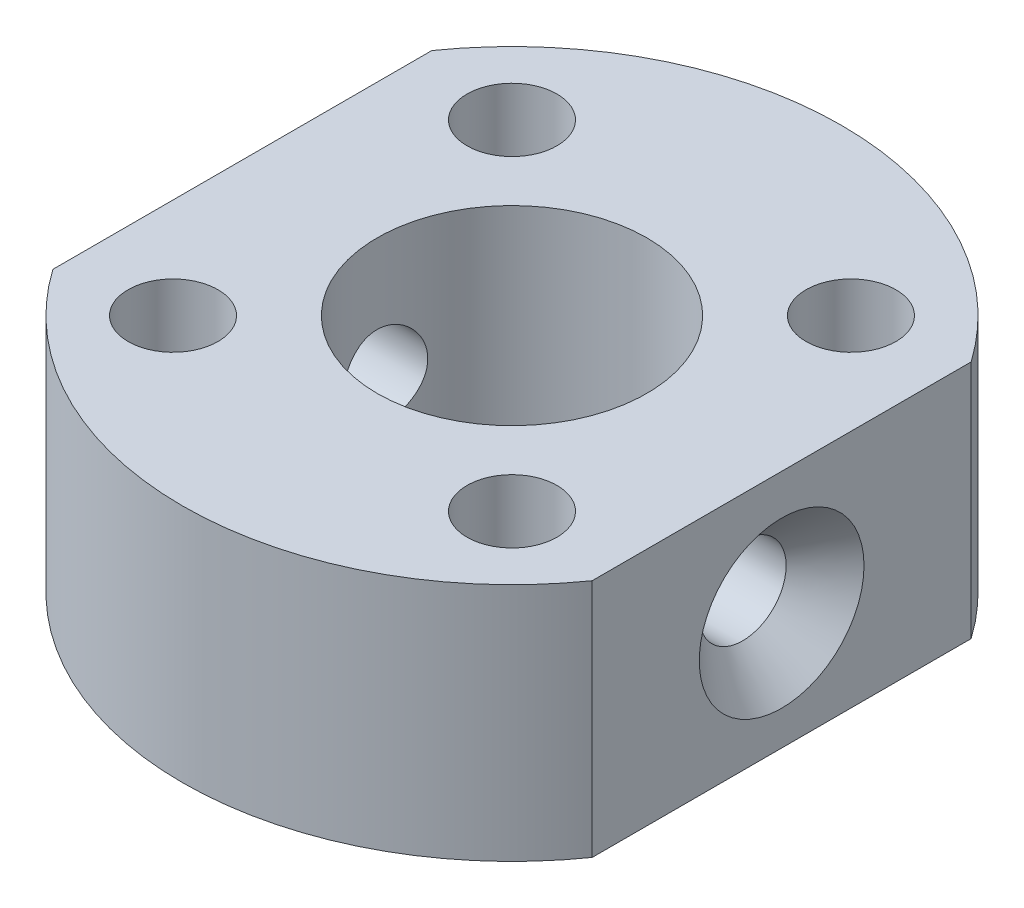
SolidWorks part; units mm, degrees
ref_plane "Front Plane" through (0, 0, 0) normal (0, 0, 1) x (1, 0, 0)
ref_plane "Top Plane" through (0, 0, 0) normal (0, 1, 0) x (1, 0, 0)
ref_plane "Right Plane" through (0, 0, 0) normal (1, 0, 0) x (0, 0, -1)
sketch "Sketch2" plane through (0, 0, 0) normal (0, 1, 0) x (1, 0, 0)
  circle A0 centre (0, 0) radius 11
  dimension "D1" = 22
extrude "Boss-Extrude1" add sketch "Sketch2" along normal blind 8
sketch "Sketch3" plane through (0, 8, 0) normal (0, 1, 0) x (1, 0, 0)
  line L5 (-9, 11.5) -> (9, 11.5)
  line L6 (-9, 11.5) -> (-9, -11.5)
  line L7 (-9, -11.5) -> (9, -11.5)
  line L8 (9, 11.5) -> (9, -11.5)
  line L9 (0, -11.5) -> (0, 11.5) construction
  line L10 (-9, 0) -> (9, 0) construction
  point P0 (0, 0)
  dimension "D1" = 9
  dimension "D2" = 11.5
extrude "Cut-Extrude1" cut sketch "Sketch3" against normal blind 8 flip side to cut
hole_wizard "Ø9.0 (9) Diameter Hole1" positions "Sketch4" profile "Sketch5" hole size "Ø9.0" standard "ANSI Metric" end condition through all
sketch "Sketch4" plane through (0, 8, 0) normal (0, 1, 0) x (1, 0, 0)
  point P0 (0, 0)
sketch "Sketch5" plane through (0, 8, 0) normal (1, 0, 0) x (0, 0, 1)
  line L0 (0, 0) -> (0, 8)
  line L1 (0, 8) -> (4.5, 8)
  line L2 (4.5, 8) -> (4.5, 0)
  line L5 (4.5, 0) -> (0, 0)
  line L11 (0, -6.35) -> (0, 107.95) construction
  dimension "Thru Hole Dia." = 9
  dimension "Thru Hole Depth" = 8
hole_wizard "CSK for M2.5 Flat Head Machine Screw1" positions "Sketch7" profile "Sketch8" countersink size "M2.5" standard "ANSI Metric" end condition up to next
sketch "Sketch7" plane through (-9, 0, 0) normal (-1, 0, 0) x (0, 0, 1)
  line L0 (-6.3246, 8) -> (6.3246, 8) construction
  point P0 (0, 3.9)
  dimension "D1" = 4.1
sketch "Sketch8" plane through (-9, 3.9, 0) normal (0, 1, 0) x (0, 0, 1)
  line L0 (0, 0) -> (0, 18)
  line L1 (0, 18) -> (1.45, 18)
  line L2 (1.45, 18) -> (1.45, 1.3)
  line L3 (1.45, 1.3) -> (2.75, 0)
  line L5 (2.75, 0) -> (0, 0)
  line L6 (-1.45, 1.3) -> (-2.75, 0) construction
  line L11 (0, -6.35) -> (0, 107.95) construction
  dimension "Thru Hole Dia." = 2.9
  dimension "Thru Hole Depth" = 18
  dimension "Near C'Sink Dia." = 5.5
  dimension "Near C'Sink Angle" = 90
mirror "Mirror1" about plane through (0, 0, 0) normal (1, 0, 0) of "CSK for M2.5 Flat Head Machine Screw1"
hole_wizard "Ø3.0 (3) Diameter Hole1" positions "Sketch9" profile "Sketch10" hole size "Ø3.0" standard "ANSI Metric"
sketch "Sketch9" plane through (0, 8, 0) normal (0, 1, 0) x (1, 0, 0)
  line L0 (0, 0) -> (-5.6569, 5.6569) construction
  line L2 (-9, 6.3246) -> (-9, -6.3246) construction
  circle A0 centre (0, 0) radius 8 construction
  point P0 (-5.6569, 5.6569)
  dimension "D1" = 16
  dimension "D2" = 45
sketch "Sketch10" plane through (-5.6569, 8, -5.6569) normal (1, 0, 0) x (0, 0, 1)
  line L0 (0, 0) -> (0, 6.9013)
  line L1 (0, 6.9013) -> (1.5, 6)
  line L2 (1.5, 6) -> (1.5, 0)
  line L5 (1.5, 0) -> (0, 0)
  line L10 (0, 6.9013) -> (-1.5, 6) construction
  line L11 (0, -6.35) -> (0, 107.95) construction
  dimension "Hole Dia." = 3
  dimension "Hole Depth" = 6
  dimension "Drill Angle" = 118
pattern_circular "CirPattern1" count 4 over 360 about axis through (0, 8, 0) along (0, 1, 0) of "Ø3.0 (3) Diameter Hole1"
